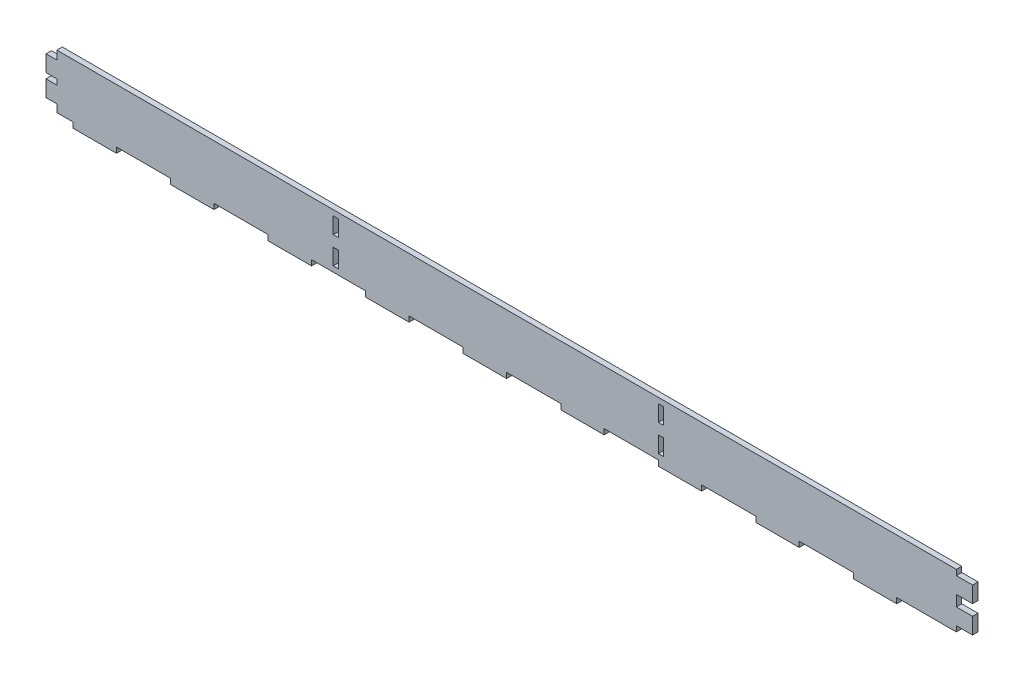
SolidWorks part; units mm, degrees
ref_plane "Front Plane" through (0, 0, 0) normal (0, 0, 1) x (1, 0, 0)
ref_plane "Top Plane" through (0, 0, 0) normal (0, 1, 0) x (1, 0, 0)
ref_plane "Right Plane" through (0, 0, 0) normal (1, 0, 0) x (0, 0, -1)
sketch "Model" plane through (0, 0, 0) normal (0, 0, 1) x (1, 0, 0)
  line L0 (-590, 20) -> (-590, 5)
  line L1 (-590, 5) -> (-585, 5)
  line L2 (-585, 5) -> (-585, 20)
  line L3 (-585, 20) -> (-590, 20)
  line L4 (610, 20) -> (610, 5)
  line L5 (610, 5) -> (615, 5)
  line L6 (615, 5) -> (615, 20)
  line L7 (615, 20) -> (610, 20)
  line L8 (-590, 45) -> (-590, 30)
  line L9 (-590, 30) -> (-585, 30)
  line L10 (-585, 30) -> (-585, 45)
  line L11 (-585, 45) -> (-590, 45)
  line L12 (610, 45) -> (610, 30)
  line L13 (610, 30) -> (615, 30)
  line L14 (615, 30) -> (615, 45)
  line L15 (615, 45) -> (610, 45)
  line L16 (310, 20) -> (310, 5)
  line L17 (310, 5) -> (315, 5)
  line L18 (315, 5) -> (315, 20)
  line L19 (315, 20) -> (310, 20)
  line L20 (310, 45) -> (310, 30)
  line L21 (310, 30) -> (315, 30)
  line L22 (315, 30) -> (315, 45)
  line L23 (315, 45) -> (310, 45)
  line L24 (10, 20) -> (10, 5)
  line L25 (10, 5) -> (15, 5)
  line L26 (15, 5) -> (15, 20)
  line L27 (15, 20) -> (10, 20)
  line L28 (10, 45) -> (10, 30)
  line L29 (10, 30) -> (15, 30)
  line L30 (15, 30) -> (15, 45)
  line L31 (15, 45) -> (10, 45)
  line L32 (-290, 20) -> (-290, 5)
  line L33 (-290, 5) -> (-285, 5)
  line L34 (-285, 5) -> (-285, 20)
  line L35 (-290, 45) -> (-290, 30)
  line L36 (-290, 30) -> (-285, 30)
  line L37 (-285, 30) -> (-285, 45)
  line L38 (-285, 45) -> (-290, 45)
  line L39 (-285, 20) -> (-290, 20)
  line L40 (-885, 0) -> (-830, 0)
  line L41 (-830, 0) -> (-830, -5)
  line L42 (-830, -5) -> (-790, -5)
  line L43 (-790, -5) -> (-790, 0)
  line L44 (-790, 0) -> (-740, 0)
  line L45 (-740, 0) -> (-740, -5)
  line L46 (-740, -5) -> (-700, -5)
  line L47 (-700, -5) -> (-700, 0)
  line L48 (-700, 0) -> (-650, 0)
  line L49 (-650, 0) -> (-650, -5)
  line L50 (-650, -5) -> (-610, -5)
  line L51 (-610, -5) -> (-610, 0)
  line L52 (-610, 0) -> (-560, 0)
  line L53 (-560, 0) -> (-560, -5)
  line L54 (-560, -5) -> (-520, -5)
  line L55 (-520, -5) -> (-520, 0)
  line L56 (-520, 0) -> (-470, 0)
  line L57 (-470, 0) -> (-470, -5)
  line L58 (-470, -5) -> (-430, -5)
  line L59 (-430, -5) -> (-430, 0)
  line L60 (-430, 0) -> (-380, 0)
  line L61 (-380, 0) -> (-380, -5)
  line L62 (-380, -5) -> (-340, -5)
  line L63 (-340, -5) -> (-340, 0)
  line L64 (-340, 0) -> (-290, 0)
  line L65 (-290, 0) -> (-290, -5)
  line L66 (-290, -5) -> (-250, -5)
  line L67 (-250, -5) -> (-250, 0)
  line L68 (-250, 0) -> (-200, 0)
  line L69 (-200, 0) -> (-200, -5)
  line L70 (-200, -5) -> (-160, -5)
  line L71 (-160, -5) -> (-160, 0)
  line L72 (-160, 0) -> (-110, 0)
  line L73 (-110, 0) -> (-110, -5)
  line L74 (-110, -5) -> (-70, -5)
  line L75 (-70, -5) -> (-70, 0)
  line L76 (-70, 0) -> (-20, 0)
  line L77 (-20, 0) -> (-20, -5)
  line L78 (-20, -5) -> (20, -5)
  line L79 (20, -5) -> (20, 0)
  line L80 (20, 0) -> (70, 0)
  line L81 (70, 0) -> (70, -5)
  line L82 (70, -5) -> (110, -5)
  line L83 (110, -5) -> (110, 0)
  line L84 (110, 0) -> (160, 0)
  line L85 (160, 0) -> (160, -5)
  line L86 (160, -5) -> (200, -5)
  line L87 (200, -5) -> (200, 0)
  line L88 (200, 0) -> (250, 0)
  line L89 (250, 0) -> (250, -5)
  line L90 (250, -5) -> (290, -5)
  line L91 (290, -5) -> (290, 0)
  line L92 (290, 0) -> (340, 0)
  line L93 (340, 0) -> (340, -5)
  line L94 (340, -5) -> (380, -5)
  line L95 (380, -5) -> (380, 0)
  line L96 (380, 0) -> (430, 0)
  line L97 (430, 0) -> (430, -5)
  line L98 (430, -5) -> (470, -5)
  line L99 (470, -5) -> (470, 0)
  line L100 (470, 0) -> (520, 0)
  line L101 (520, 0) -> (520, -5)
  line L102 (520, -5) -> (560, -5)
  line L103 (560, -5) -> (560, 0)
  line L104 (560, 0) -> (610, 0)
  line L105 (610, 0) -> (610, -5)
  line L106 (610, -5) -> (650, -5)
  line L107 (650, -5) -> (650, 0)
  line L108 (650, 0) -> (700, 0)
  line L109 (700, 0) -> (700, -5)
  line L110 (700, -5) -> (740, -5)
  line L111 (740, -5) -> (740, 0)
  line L112 (740, 0) -> (790, 0)
  line L113 (790, 0) -> (790, -5)
  line L114 (790, -5) -> (830, -5)
  line L115 (830, -5) -> (830, 0)
  line L116 (830, 0) -> (885, 0)
  line L117 (885, 0) -> (885, 5)
  line L118 (885, 5) -> (900, 5)
  line L119 (900, 5) -> (900, 20)
  line L120 (900, 20) -> (885, 20)
  line L121 (885, 20) -> (885, 30)
  line L122 (885, 30) -> (900, 30)
  line L123 (900, 30) -> (900, 45)
  line L124 (900, 45) -> (885, 45)
  line L125 (885, 45) -> (885, 50)
  line L126 (885, 50) -> (-885, 50)
  line L127 (-885, 50) -> (-885, 45)
  line L128 (-885, 45) -> (-900, 45)
  line L129 (-900, 45) -> (-900, 30)
  line L130 (-900, 30) -> (-885, 30)
  line L131 (-885, 30) -> (-885, 20)
  line L132 (-885, 20) -> (-900, 20)
  line L133 (-900, 20) -> (-900, 5)
  line L134 (-900, 5) -> (-885, 5)
  line L135 (-885, 5) -> (-885, 0)
extrude "Boss-Extrude1" add sketch "Model" along normal blind 5
sketch "Sketch1" plane through (0, 0, 5) normal (0, 0, 1) x (1, 0, 0)
  line L0 (55, 50) -> (55, 42)
  line L1 (885, 50) -> (-885, 50) construction
  line L2 (55, 42) -> (45, 42)
  line L3 (45, 42) -> (45, 27)
  line L4 (45, 27) -> (55, 27)
  line L5 (55, 27) -> (55, 22)
  line L6 (55, 22) -> (45, 22)
  line L7 (45, 22) -> (45, 7)
  line L8 (45, 7) -> (55, 7)
  line L9 (55, 7) -> (55, 0)
  line L10 (20, 0) -> (70, 0) construction
  line L14 (55, 50) -> (-1184.2193, 174.4728)
  line L15 (-1184.2193, 174.4728) -> (-782.7438, -337.8579)
  line L16 (-782.7438, -337.8579) -> (55, 0)
  dimension "D1" = 5
  dimension "D2" = 10
  dimension "D3" = 10
  dimension "D4" = 10
  dimension "D5" = 10
  dimension "D6" = 8
  dimension "D7" = 15
  dimension "D8" = 15
  dimension "D9" = 35
extrude "Cut-Extrude1" cut sketch "Sketch1" against normal through all
